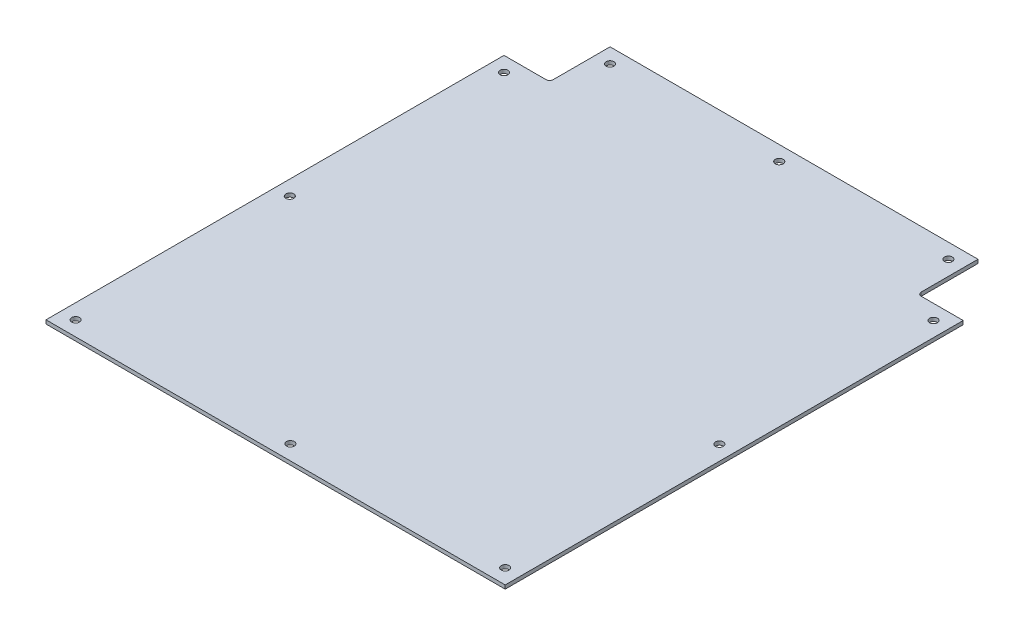
SolidWorks part; units mm, degrees
material "6061-T6 (SS)"
ref_plane "Front" through (0, 0, 0) normal (0, 0, 1) x (1, 0, 0)
ref_plane "Top" through (0, 0, 0) normal (0, 1, 0) x (1, 0, 0)
ref_plane "Right" through (0, 0, 0) normal (1, 0, 0) x (0, 0, -1)
sketch "Sketch1" plane through (0, 0, 0) normal (0, 1, 0) x (1, 0, 0)
  line L1 (196.85, -222.25) -> (-196.85, -222.25)
  line L2 (196.85, -222.25) -> (196.85, 222.25)
  line L3 (196.85, 222.25) -> (-196.85, 222.25)
  line L4 (-196.85, -222.25) -> (-196.85, 222.25)
  line L5 (196.85, -222.25) -> (-196.85, 222.25) construction
  line L6 (196.85, 222.25) -> (-196.85, -222.25) construction
  point P0 (0, 0)
  dimension "D1" = 393.7
  dimension "D2" = 444.5
extrude "Boss-Extrude1" add sketch "Sketch1" along normal blind 3.175
sketch "Sketch2" plane through (0, 3.175, 0) normal (0, 1, 0) x (1, 0, 0)
  line L0 (196.85, 222.25) -> (-196.85, 222.25) construction
  line L1 (-196.85, 222.25) -> (-157.734, 222.25)
  line L2 (-196.85, 222.25) -> (-196.85, 170.434)
  line L3 (-196.85, 170.434) -> (-160.909, 170.434)
  line L4 (-157.734, 222.25) -> (-157.734, 173.609)
  line L5 (196.85, 222.25) -> (157.734, 222.25)
  line L6 (196.85, 222.25) -> (196.85, 170.434)
  line L7 (196.85, 170.434) -> (160.909, 170.434)
  line L8 (157.734, 222.25) -> (157.734, 173.609)
  arc A0 (-157.734, 173.609) -> (-160.909, 170.434) centre (-160.909, 173.609) cw
  arc A1 (157.734, 173.609) -> (160.909, 170.434) centre (160.909, 173.609) ccw
  dimension "D1" = 3.175
  dimension "D2" = 51.816
  dimension "D3" = 39.116
extrude "Cut-Extrude1" cut sketch "Sketch2" against normal blind 10
hole_wizard "1/4 Clearance Hole1" positions "Sketch3" profile "Sketch4" hole size "1/4" standard "ANSI Inch"
sketch "Sketch3" plane through (0, 3.175, 0) normal (0, 1, 0) x (1, 0, 0)
  line L0 (184.15, -209.55) -> (0, -209.55) construction
  line L1 (0, -209.55) -> (-184.15, -209.55) construction
  line L2 (-184.15, -209.55) -> (-184.15, -25.908) construction
  line L3 (-184.15, -25.908) -> (-184.15, 157.734) construction
  line L4 (-184.15, 157.734) -> (184.15, 157.734) construction
  line L5 (184.15, 157.734) -> (184.15, -25.908) construction
  line L6 (184.15, -25.908) -> (184.15, -209.55) construction
  line L8 (145.034, 209.55) -> (0, 209.55) construction
  line L9 (0, 209.55) -> (-145.034, 209.55) construction
  line L10 (-145.034, 209.55) -> (-157.734, 222.25) construction
  line L12 (157.734, 222.25) -> (145.034, 209.55) construction
  line L14 (-184.15, 157.734) -> (-196.85, 170.434) construction
  line L16 (-184.15, -209.55) -> (-196.85, -222.25) construction
  line L18 (184.15, 157.734) -> (196.85, 170.434) construction
  line L20 (184.15, -209.55) -> (196.85, -222.25) construction
  line L21 (184.15, -209.55) -> (184.15, -222.25) construction
  line L22 (-196.85, -222.25) -> (196.85, -222.25) construction
  line L24 (184.15, -209.55) -> (196.85, -209.55) construction
  line L25 (196.85, -222.25) -> (196.85, 170.434) construction
  point P0 (184.15, -209.55)
  point P2 (-184.15, -209.55)
  point P4 (-184.15, 157.734)
  point P6 (-145.034, 209.55)
  point P8 (145.034, 209.55)
  point P10 (184.15, 157.734)
  point P12 (184.15, -25.908)
  point P14 (0, -209.55)
  point P16 (-184.15, -25.908)
  point P18 (0, 209.55)
  dimension "D1" = 12.7
sketch "Sketch4" plane through (184.15, 3.175, 209.55) normal (1, 0, 0) x (0, 0, 1)
  line L0 (0, 0) -> (0, 20.7798)
  line L1 (0, 20.7798) -> (3.3782, 18.75)
  line L2 (3.3782, 18.75) -> (3.3782, 0)
  line L5 (3.3782, 0) -> (0, 0)
  line L10 (0, 20.7798) -> (-3.3782, 18.75) construction
  line L11 (0, -6.35) -> (0, 107.95) construction
  dimension "Hole Dia." = 6.7564
  dimension "Hole Depth" = 18.75
  dimension "Drill Angle" = 118
